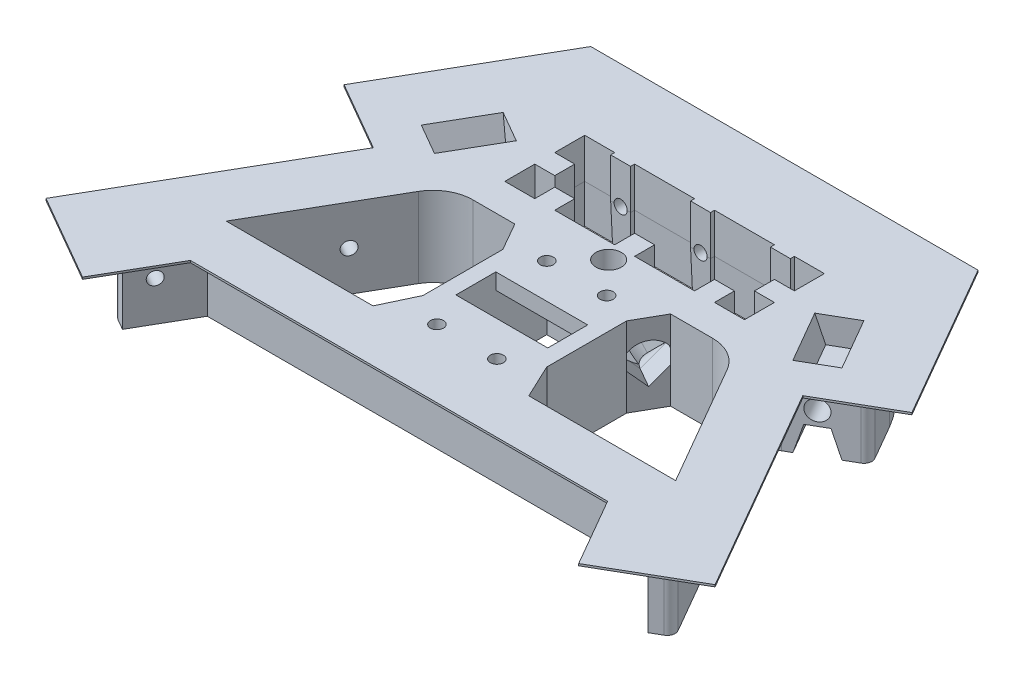
SolidWorks part; units mm, degrees
ref_plane "Front Plane" through (0, 0, 0) normal (0, 0, 1) x (1, 0, 0)
ref_plane "Top Plane" through (0, 0, 0) normal (0, 1, 0) x (1, 0, 0)
ref_plane "Right Plane" through (0, 0, 0) normal (1, 0, 0) x (0, 0, -1)
sketch "Sketch1" plane through (0, 0, 0) normal (0, 1, 0) x (1, 0, 0)
  line L0 (-30, -18) -> (30, -18)
  line L1 (-30, 10) -> (-22.5, 10)
  line L2 (-46.46, 5.4904) -> (-53.96, -7.5) construction
  line L3 (-30, -10) -> (-22.5, -10)
  line L4 (30, 10) -> (30, 2.5)
  line L5 (0, 0) -> (0, -75.5561) construction
  line L6 (38.6603, -23) -> (65.7735, -69.9615)
  line L7 (65.7735, -69.9615) -> (68.3716, -68.4615)
  line L8 (69.1036, -65.7295) -> (41.8357, -18.5)
  line L9 (43.1036, -13.7679) -> (55.6921, -6.5)
  line L10 (56.4241, -3.7679) -> (51.362, 5)
  line L11 (25.3812, 20) -> (-25.3812, 20)
  line L12 (43.5677, -13.5) -> (36.0677, -0.5096) construction
  line L13 (36.0677, -0.5096) -> (46.46, 5.4904) construction
  line L14 (46.46, 5.4904) -> (53.96, -7.5) construction
  line L15 (-36.0677, -0.5096) -> (-46.46, 5.4904) construction
  line L16 (-43.5677, -13.5) -> (-36.0677, -0.5096) construction
  line L17 (-56.4241, -3.7679) -> (-51.362, 5)
  line L18 (-43.1036, -13.7679) -> (-55.6921, -6.5)
  line L19 (-69.1036, -65.7295) -> (-41.8357, -18.5)
  line L20 (-65.7735, -69.9615) -> (-68.3716, -68.4615)
  line L21 (-38.6603, -23) -> (-65.7735, -69.9615)
  line L22 (-30, 10) -> (-30, 2.5)
  line L23 (30, 2.5) -> (25, 2.5)
  line L24 (25, 2.5) -> (25, -2.5)
  line L25 (25, -2.5) -> (30, -2.5)
  line L26 (30, -2.5) -> (30, -10)
  line L27 (22.5, -10) -> (22.5, -5)
  line L28 (22.5, -5) -> (17.5, -5)
  line L29 (17.5, -5) -> (17.5, -10)
  line L30 (22.5, -10) -> (30, -10)
  line L31 (17.5, 10) -> (17.5, 9)
  line L32 (17.5, 9) -> (22.5, 9)
  line L33 (22.5, 9) -> (22.5, 10)
  line L34 (22.5, 10) -> (30, 10)
  line L35 (2.5, -10) -> (2.5, -5)
  line L36 (2.5, -5) -> (-2.5, -5)
  line L37 (-2.5, -5) -> (-2.5, -10)
  line L38 (-2.5, 10) -> (-2.5, 9)
  line L39 (-2.5, 9) -> (2.5, 9)
  line L40 (2.5, 9) -> (2.5, 10)
  line L41 (-17.5, -10) -> (-17.5, -5)
  line L42 (-17.5, -5) -> (-22.5, -5)
  line L43 (-22.5, -5) -> (-22.5, -10)
  line L44 (-22.5, 10) -> (-22.5, 9)
  line L45 (-22.5, 9) -> (-17.5, 9)
  line L46 (-17.5, 9) -> (-17.5, 10)
  line L47 (-17.5, 10) -> (-2.5, 10)
  line L48 (-17.5, -10) -> (-2.5, -10)
  line L49 (2.5, -10) -> (17.5, -10)
  line L50 (2.5, 10) -> (17.5, 10)
  line L51 (-25, -2.5) -> (-30, -2.5)
  line L52 (-25, 2.5) -> (-25, -2.5)
  line L53 (-30, 2.5) -> (-25, 2.5)
  line L54 (-30, -2.5) -> (-30, -10)
  circle A0 centre (0, 0) radius 31.6228 construction
  arc A1 (30, -18) -> (38.6603, -23) centre (30, -28) cw
  arc A2 (51.362, 5) -> (25.3812, 20) centre (25.3812, -10) ccw
  arc A3 (41.1036, -13.7679) -> (40.1036, -17.5) centre (40.1036, -15.5) ccw
  arc A4 (68.3716, -68.4615) -> (69.1036, -65.7295) centre (67.3716, -66.7295) ccw
  arc A5 (55.6921, -6.5) -> (56.4241, -3.7679) centre (54.6921, -4.7679) ccw
  arc A6 (40.1036, -17.5) -> (41.8357, -18.5) centre (40.1036, -19.5) cw
  arc A7 (41.1036, -13.7679) -> (43.1036, -13.7679) centre (42.1036, -12.0359) ccw
  arc A8 (-41.1036, -13.7679) -> (-43.1036, -13.7679) centre (-42.1036, -12.0359) cw
  arc A9 (-40.1036, -17.5) -> (-41.8357, -18.5) centre (-40.1036, -19.5) ccw
  arc A10 (-55.6921, -6.5) -> (-56.4241, -3.7679) centre (-54.6921, -4.7679) cw
  arc A11 (-68.3716, -68.4615) -> (-69.1036, -65.7295) centre (-67.3716, -66.7295) cw
  arc A12 (-41.1036, -13.7679) -> (-40.1036, -17.5) centre (-40.1036, -15.5) cw
  arc A13 (-51.362, 5) -> (-25.3812, 20) centre (-25.3812, -10) cw
  arc A14 (-30, -18) -> (-38.6603, -23) centre (-30, -28) ccw
  point P7 (-57.4241, -5.5)
  point P9 (0, -18)
  point P22 (35.7735, -18)
  point P27 (0, 10)
  point P30 (70.1036, -67.4615)
  point P33 (57.4241, -5.5)
  point P61 (0, 20)
  point P65 (-70.1036, -67.4615)
  point P66 (-35.7735, -18)
  dimension "D12" = 10
  dimension "D14" = 30
  dimension "D16" = 2
  dimension "D17" = 2
  dimension "D2" = 30
  dimension "D3" = 5
  dimension "D4" = 8
  dimension "D5" = 60
  dimension "D6" = 20
  dimension "D7" = 30
  dimension "D8" = 10
  dimension "D9" = 4
  dimension "D10" = 12
  dimension "D11" = 15
  dimension "D13" = 20
  dimension "D18" = 5
  dimension "D19" = 2.5
  dimension "D20" = 5
  dimension "D21" = 5
  dimension "D22" = 5
  dimension "D23" = 7.5
  dimension "D24" = 1
  dimension "D26" = 20
  dimension "D25" = 3
extrude "Boss-Extrude1" add sketch "Sketch1" along normal blind 20
sketch "Sketch2" plane through (16.7376, 0, 28.9904) normal (0.5, 0, 0.866) x (0.866, 0, -0.5)
  line L0 (30.4449, 0) -> (44.9808, 0) construction
  line L1 (26.9808, 20) -> (26.9808, 0) construction
  circle A0 centre (36.9808, 10) radius 5
  dimension "D1" = 10
  dimension "D2" = 10
  dimension "D3" = 10
extrude "Cut-Extrude1" cut sketch "Sketch2" against normal through all
sketch "Sketch3" plane through (16.7376, 0, 28.9904) normal (0.5, 0, 0.866) x (0.866, 0, -0.5)
  circle A0 centre (36.9808, 10) radius 5
  circle A1 centre (36.9808, 10) radius 5 construction
  circle A2 centre (36.9808, 10) radius 2.5
  dimension "D1" = 5
extrude "Boss-Extrude2" add sketch "Sketch3" against normal blind 16
sketch "Sketch4" plane through (16.7376, 0, 28.9904) normal (0.5, 0, 0.866) x (0.866, 0, -0.5)
  line L0 (36.9808, 10) -> (44.9808, 10) construction
  line L1 (44.9808, 20) -> (44.9808, 0) construction
  line L2 (32.4808, 20) -> (34.4808, 13.5)
  line L3 (30.4449, 20) -> (44.9808, 20) construction
  line L4 (34.4808, 13.5) -> (39.4808, 13.5)
  line L5 (39.4808, 13.5) -> (41.4808, 20)
  line L6 (41.4808, 20) -> (32.4808, 20)
  line L7 (36.9808, 13.5) -> (36.9808, 20) construction
  line L8 (41.4808, 0) -> (32.4808, 0)
  line L9 (39.4808, 6.5) -> (41.4808, 0)
  line L10 (34.4808, 6.5) -> (39.4808, 6.5)
  line L11 (32.4808, 0) -> (34.4808, 6.5)
  dimension "D1" = 9
  dimension "D2" = 5
  dimension "D3" = 6.5
extrude "Cut-Extrude2" cut sketch "Sketch4" against normal blind 15
sketch "Sketch7" plane through (0, 0, -20) normal (0, 0, -1) x (-1, 0, 0)
  line L0 (-20, 10) -> (20, 10) construction
  circle A0 centre (-20, 10) radius 1.65
  circle A1 centre (0, 10) radius 1.65
  circle A2 centre (20, 10) radius 1.65
  dimension "D1" = 3.3
  dimension "D3" = 40
  dimension "D4" = 10
  dimension "D2" = 3
extrude "Cut-Extrude4" cut sketch "Sketch7" against normal up to next
sketch "Sketch8" plane through (0, 0, -20) normal (0, 0, -1) x (-1, 0, 0)
  circle A0 centre (-20, 10) radius 6
  circle A1 centre (-20, 10) radius 1.65 construction
  circle A2 centre (0, 10) radius 6
  circle A3 centre (20, 10) radius 6
  circle A4 centre (20, 10) radius 1.65 construction
  dimension "D1" = 12
  dimension "D2" = 3
extrude "Cut-Extrude5" cut sketch "Sketch8" against normal offset from surface (4 mm away) 7 up to face at (1.65, 10, -9)
sketch "Sketch9" plane through (0, 0, 0) normal (0, 1, 0) x (1, 0, 0)
  line L0 (-11.5, -40) -> (11.5, -40) construction
  line L1 (2.5, -10) -> (17.5, -10) construction
  line L2 (-11.5, -30) -> (11.5, -30) construction
  line L3 (-11.5, -30) -> (-11.5, -40)
  line L4 (11.5, -30) -> (11.5, -40)
  line L5 (0, -30) -> (0, 0) construction
  line L6 (-19.5, -18) -> (-15.5, -25)
  line L7 (-30, -18) -> (30, -18) construction
  line L8 (-15.5, -25) -> (-15.5, -45)
  line L9 (-15.5, -45) -> (-19.5, -53.5)
  line L10 (-56.2694, -53.5) -> (-19.5, -53.5)
  line L11 (19.5, -53.5) -> (15.5, -45)
  line L12 (15.5, -45) -> (15.5, -25)
  line L13 (15.5, -25) -> (19.5, -18)
  line L14 (-19.5, -18) -> (-11.5, -18)
  line L15 (-11.5, -35) -> (11.5, -35) construction
  line L16 (11.5, -30) -> (11.5, -18)
  line L17 (-11.5, -30) -> (-11.5, -18)
  line L18 (11.5, -18) -> (19.5, -18)
  line L19 (-11.5, -40) -> (-11.5, -53.5)
  line L20 (-11.5, -53.5) -> (11.5, -53.5)
  line L21 (11.5, -53.5) -> (11.5, -40)
  line L30 (-65.7735, -69.9615) -> (-38.6603, -23) construction
  line L31 (38.6603, -23) -> (65.7735, -69.9615) construction
  line L32 (19.5, -53.5) -> (56.2694, -53.5)
  line L33 (-58.0015, -56.5) -> (58.0015, -56.5)
  line L34 (58.0015, -56.5) -> (56.2694, -53.5)
  line L35 (-58.0015, -56.5) -> (-56.2694, -53.5)
  circle A0 centre (0, -20.5) radius 1.65 construction
  circle A1 centre (0, -49.5) radius 1.65 construction
  dimension "D6" = 3.3
  dimension "D11" = 2.5
  dimension "D1" = 30
  dimension "D2" = 10
  dimension "D3" = 23
  dimension "D4" = 4
  dimension "D5" = 4
  dimension "D7" = 7
  dimension "D8" = 8.5
  dimension "D9" = 7
  dimension "D10" = 20
  dimension "D14" = 4
  dimension "D15" = 4
  dimension "D16" = 4
  dimension "D17" = 3
extrude "Boss-Extrude3" add sketch "Sketch9" along normal up to surface (20 mm away) up to face at (6.0019, 20, 19.8008)
sketch "Sketch11" plane through (23.366, 0, -13.4904) normal (0.866, 0, -0.5) x (-0.5, 0, -0.866)
  line L1 (-81.4752, 12.5) -> (-56.9393, 12.5)
  line L2 (-81.4752, 12.5) -> (-81.4752, 7.5)
  line L3 (-81.4752, 7.5) -> (-56.9393, 7.5)
  line L4 (-36.9393, 12.5) -> (-36.9393, 7.5)
  line L5 (-36.9393, 20) -> (-36.9393, 0) construction
  line L6 (-91.4752, 0) -> (-36.9393, 0) construction
  line L7 (-46.9393, 12.5) -> (-46.9393, 7.5)
  line L8 (-56.9393, 12.5) -> (-56.9393, 7.5)
  line L9 (-46.9393, 12.5) -> (-36.9393, 12.5)
  line L10 (-46.9393, 7.5) -> (-36.9393, 7.5)
  line L11 (-91.4752, 20) -> (-91.4752, 0) construction
  dimension "D1" = 5
  dimension "D2" = 7.5
  dimension "D3" = 10
  dimension "D4" = 10
  dimension "D5" = 10
extrude "Boss-Extrude5" add sketch "Sketch11" along normal blind 3
chamfer "Chamfer1" distance 3 angle 45 4 edges at (44.4338, 10, 17) (49.4338, 10, 25.6603) (54.4338, 10, 34.3205) (66.7017, 10, 55.5692)
sketch "Sketch13" plane through (23.366, 0, -13.4904) normal (0.866, 0, -0.5) x (-0.5, 0, -0.866)
  line L0 (-56.9393, 10) -> (-46.9393, 10) construction
  line L1 (-56.9393, 7.5) -> (-56.9393, 12.5) construction
  line L2 (-46.9393, 12.5) -> (-46.9393, 7.5) construction
  line L3 (-81.4752, 10) -> (-93.4752, 10) construction
  line L4 (-81.4752, 12.5) -> (-81.4752, 7.5) construction
  line L5 (-93.4752, 20) -> (-93.4752, 0) construction
  circle A0 centre (-51.9393, 10) radius 1.65
  circle A1 centre (-87.4752, 10) radius 1.65
  dimension "D1" = 3.3
  dimension "D2" = 3.3
extrude "Cut-Extrude6" cut sketch "Sketch13" against normal up to next
mirror "Mirror2" about plane through (0, 0, 0) normal (1, 0, 0) of "Cut-Extrude6", "Chamfer1", "Boss-Extrude5", "Cut-Extrude2", "Boss-Extrude2", "Cut-Extrude1"
ref_plane "Plane2" through (0, 10, 0) normal (0, 1, 0) x (1, 0, 0)
sketch "Sketch15" plane through (0, 10, 0) normal (0, 1, 0) x (1, 0, 0)
  line L0 (-10, -10) -> (-10, -14.3127)
  line L1 (-17.5, -10) -> (-2.5, -10) construction
  line L2 (-12.5193, -18.6539) -> (-17.5, -21.5)
  line L3 (-19.5, -18) -> (-15.5, -25) construction
  arc A0 (-10, -14.3127) -> (-12.5193, -18.6539) centre (-15, -14.3127) cw
  dimension "D1" = 5
sketch "Sketch16" plane through (0, 0, 10) normal (0, 0, -1) x (-1, 0, 0)
  line L0 (5, 10) -> (10, 5)
  line L1 (10, 5) -> (15, 10)
  arc A0 (15, 10) -> (5, 10) centre (10, 10) ccw
  dimension "D1" = 10
sketch "Sketch17" plane through (0, 20, 0) normal (0, 1, 0) x (1, 0, 0)
  line L0 (-11.5, -53.5) -> (-11.5, -18) construction
  line L1 (11.5, -18) -> (-11.5, -18)
  line L2 (11.5, -18) -> (11.5, -30.75)
  line L3 (11.5, -30.75) -> (-11.5, -30.75)
  line L4 (-11.5, -18) -> (-11.5, -30.75)
  line L5 (-11.5, -18) -> (11.5, -18) construction
  line L6 (11.5, -18) -> (11.5, -53.5) construction
  line L7 (11.5, -53.5) -> (-11.5, -53.5) construction
  line L9 (-11.5, -53.5) -> (11.5, -53.5)
  line L10 (-11.5, -53.5) -> (-11.5, -40.75)
  line L11 (-11.5, -40.75) -> (11.5, -40.75)
  line L12 (11.5, -53.5) -> (11.5, -40.75)
  line L13 (22.5, -10) -> (30, -10) construction
  circle A0 centre (-7.5, -49.5) radius 1.65
  circle A1 centre (7.5, -49.5) radius 1.65
  circle A2 centre (7.5, -22) radius 1.65
  circle A3 centre (-7.5, -22) radius 1.65
  dimension "D3" = 3.3
  dimension "D4" = 4
  dimension "D5" = 4
  dimension "D8" = 4
  dimension "D1" = 10
  dimension "D2" = 30.75
  dimension "D9" = 4
  dimension "D6" = 2
  dimension "D7" = 2
extrude "Boss-Extrude6" add sketch "Sketch17" against normal blind 4 separate body
sweep "Cut-Sweep1" cut profiles "Sketch16" path "Sketch15"
mirror "Mirror3" about plane through (0, 0, 0) normal (1, 0, 0) of "Cut-Sweep1"
sketch "Sketch18" plane through (0, 20, 0) normal (0, 1, 0) x (1, 0, 0)
  line L0 (0, -18) -> (0, -10) construction
  line L1 (-11.5, -18) -> (11.5, -18) construction
  line L2 (2.5, -10) -> (17.5, -10) construction
  circle A0 centre (0, -14) radius 3.2
  dimension "D1" = 6.4
extrude "Cut-Extrude7" cut sketch "Sketch18" against normal blind 10
chamfer "Chamfer3" distance 10 distance2 0.25 36 edges at (26.25, 0, -10) (30, 0, -6.25) (27.5, 0, -2.5) (25, 0, 0) (27.5, 0, 2.5) (30, 0, 6.25) (26.25, 0, 10) (22.5, 0, 7.5) (20, 0, 5) (17.5, 0, 7.5) (10, 0, 10) (2.5, 0, 7.5) (0, 0, 5) (-2.5, 0, 7.5) (-10, 0, 10) (-17.5, 0, 7.5) (-20, 0, 5) (-22.5, 0, 7.5) (-26.25, 0, 10) (-30, 0, 6.25) (-27.5, 0, 2.5) (-25, 0, 0) (-27.5, 0, -2.5) (-30, 0, -6.25) (-26.25, 0, -10) (-22.5, 0, -9.5) (-20, 0, -9) (-17.5, 0, -9.5) (-10, 0, -10) (-2.5, 0, -9.5) (0, 0, -9) (2.5, 0, -9.5) (10, 0, -10) (17.5, 0, -9.5) (20, 0, -9) (22.5, 0, -9.5) first distance on face at (26.25, 10, -10) first distance on face at (30, 10, -6.25) first distance on face at (27.5, 10, -2.5) first distance on face at (25, 10, 0) first distance on face at (27.5, 10, 2.5) first distance on face at (30, 10, 6.25) first distance on face at (26.25, 10, 10) first distance on face at (22.5, 10, 7.5) first distance on face at (20, 10, 5) first distance on face at (17.5, 10, 7.5) first distance on face at (10, 10, 10) first distance on face at (2.5, 10, 7.5) first distance on face at (0, 10, 5) first distance on face at (-2.5, 10, 7.5) first distance on face at (-10, 10, 10) first distance on face at (-17.5, 10, 7.5) first distance on face at (-20, 10, 5) first distance on face at (-22.5, 10, 7.5) first distance on face at (-26.25, 10, 10) first distance on face at (-30, 10, 6.25) first distance on face at (-27.5, 10, 2.5) first distance on face at (-25, 10, 0) first distance on face at (-27.5, 10, -2.5) first distance on face at (-30, 10, -6.25) first distance on face at (-26.25, 10, -10) first distance on face at (-22.5, 10, -9.5) first distance on face at (-18.35, 10, -9) first distance on face at (-17.5, 10, -9.5) first distance on face at (-10, 10, -10) first distance on face at (-2.5, 10, -9.5) first distance on face at (1.65, 10, -9) first distance on face at (2.5, 10, -9.5) first distance on face at (10, 10, -10) first distance on face at (17.5, 10, -9.5) first distance on face at (21.65, 10, -9) first distance on face at (22.5, 10, -9.5)
sketch "Sketch20" plane through (0, 20, 0) normal (0, 1, 0) x (1, 0, 0)
  line L0 (-51.362, 5) -> (-56.4241, -3.7679) construction
  line L1 (-55.6921, -6.5) -> (-52.661, -8.25) construction
  line L2 (-50.9289, -9.25) -> (-52.661, -8.25) construction
  line L3 (-46.5988, -11.75) -> (-50.9289, -9.25) construction
  line L4 (-44.8668, -12.75) -> (-46.5988, -11.75) construction
  line L5 (-44.8668, -12.75) -> (-43.1036, -13.7679) construction
  line L6 (-41.8357, -18.5) -> (-69.1036, -65.7295) construction
  line L7 (25.3812, 20) -> (-25.3812, 20) construction
  line L44 (56.4241, -3.7679) -> (51.362, 5) construction
  line L45 (52.661, -8.25) -> (55.6921, -6.5) construction
  line L46 (50.9289, -9.25) -> (52.661, -8.25) construction
  line L47 (46.5988, -11.75) -> (50.9289, -9.25) construction
  line L48 (44.8668, -12.75) -> (46.5988, -11.75) construction
  line L49 (43.1036, -13.7679) -> (44.8668, -12.75) construction
  line L50 (69.1036, -65.7295) -> (41.8357, -18.5) construction
  line L51 (65.7735, -69.9615) -> (68.3716, -68.4615) construction
  line L52 (58.0015, -56.5) -> (65.7735, -69.9615) construction
  line L53 (-58.0015, -56.5) -> (58.0015, -56.5) construction
  line L54 (-65.7735, -69.9615) -> (-58.0015, -56.5) construction
  line L55 (-68.3716, -68.4615) -> (-65.7735, -69.9615) construction
  line L56 (-51.362, 5) -> (-56.4241, -3.7679)
  line L57 (-55.6921, -6.5) -> (-52.661, -8.25)
  line L58 (-50.9289, -9.25) -> (-52.661, -8.25)
  line L59 (-46.5988, -11.75) -> (-50.9289, -9.25)
  line L60 (-44.8668, -12.75) -> (-46.5988, -11.75)
  line L61 (-44.8668, -12.75) -> (-43.1036, -13.7679)
  line L62 (-41.8357, -18.5) -> (-69.1036, -65.7295)
  line L63 (25.3812, 20) -> (-25.3812, 20)
  line L100 (56.4241, -3.7679) -> (51.362, 5)
  line L101 (52.661, -8.25) -> (55.6921, -6.5)
  line L102 (50.9289, -9.25) -> (52.661, -8.25)
  line L103 (46.5988, -11.75) -> (50.9289, -9.25)
  line L104 (44.8668, -12.75) -> (46.5988, -11.75)
  line L105 (43.1036, -13.7679) -> (44.8668, -12.75)
  line L106 (69.1036, -65.7295) -> (41.8357, -18.5)
  line L107 (65.7735, -69.9615) -> (68.3716, -68.4615)
  line L108 (58.0015, -56.5) -> (65.7735, -69.9615)
  line L109 (-58.0015, -56.5) -> (58.0015, -56.5)
  line L110 (-65.7735, -69.9615) -> (-58.0015, -56.5)
  line L111 (-68.3716, -68.4615) -> (-65.7735, -69.9615)
  line L112 (-83.7639, -71.1218) -> (-62.1132, -83.6218)
  line L113 (-62.1132, -83.6218) -> (-52.228, -66.5)
  line L114 (-52.228, -66.5) -> (52.228, -66.5)
  line L115 (-83.7639, -71.1218) -> (-53.7639, -19.1603)
  line L116 (-53.7639, -19.1603) -> (-71.0844, -9.1603)
  line L117 (-71.0844, -9.1603) -> (-48.4752, 30)
  line L118 (-48.4752, 30) -> (48.4752, 30)
  line L119 (0, 0) -> (0, -66.5) construction
  line L120 (71.0844, -9.1603) -> (48.4752, 30)
  line L121 (53.7639, -19.1603) -> (71.0844, -9.1603)
  line L122 (83.7639, -71.1218) -> (53.7639, -19.1603)
  line L123 (83.7639, -71.1218) -> (62.1132, -83.6218)
  line L124 (62.1132, -83.6218) -> (52.228, -66.5)
  arc A0 (-56.4241, -3.7679) -> (-55.6921, -6.5) centre (-54.6921, -4.7679) ccw construction
  arc A1 (-43.1036, -13.7679) -> (-41.1036, -13.7679) centre (-42.1036, -12.0359) ccw construction
  arc A2 (-40.1036, -17.5) -> (-41.1036, -13.7679) centre (-40.1036, -15.5) ccw construction
  arc A3 (-40.1036, -17.5) -> (-41.8357, -18.5) centre (-40.1036, -19.5) ccw construction
  arc A4 (-25.3812, 20) -> (-51.362, 5) centre (-25.3812, -10) ccw construction
  arc A5 (51.362, 5) -> (25.3812, 20) centre (25.3812, -10) ccw construction
  arc A6 (55.6921, -6.5) -> (56.4241, -3.7679) centre (54.6921, -4.7679) ccw construction
  arc A7 (41.1036, -13.7679) -> (43.1036, -13.7679) centre (42.1036, -12.0359) ccw construction
  arc A8 (41.1036, -13.7679) -> (40.1036, -17.5) centre (40.1036, -15.5) ccw construction
  arc A9 (41.8357, -18.5) -> (40.1036, -17.5) centre (40.1036, -19.5) ccw construction
  arc A10 (68.3716, -68.4615) -> (69.1036, -65.7295) centre (67.3716, -66.7295) ccw construction
  arc A11 (-69.1036, -65.7295) -> (-68.3716, -68.4615) centre (-67.3716, -66.7295) ccw construction
  arc A12 (-56.4241, -3.7679) -> (-55.6921, -6.5) centre (-54.6921, -4.7679) ccw
  arc A13 (-43.1036, -13.7679) -> (-41.1036, -13.7679) centre (-42.1036, -12.0359) ccw
  arc A14 (-40.1036, -17.5) -> (-41.1036, -13.7679) centre (-40.1036, -15.5) ccw
  arc A15 (-40.1036, -17.5) -> (-41.8357, -18.5) centre (-40.1036, -19.5) ccw
  arc A16 (-25.3812, 20) -> (-51.362, 5) centre (-25.3812, -10) ccw
  arc A17 (51.362, 5) -> (25.3812, 20) centre (25.3812, -10) ccw
  arc A18 (55.6921, -6.5) -> (56.4241, -3.7679) centre (54.6921, -4.7679) ccw
  arc A19 (41.1036, -13.7679) -> (43.1036, -13.7679) centre (42.1036, -12.0359) ccw
  arc A20 (41.1036, -13.7679) -> (40.1036, -17.5) centre (40.1036, -15.5) ccw
  arc A21 (41.8357, -18.5) -> (40.1036, -17.5) centre (40.1036, -19.5) ccw
  arc A22 (68.3716, -68.4615) -> (69.1036, -65.7295) centre (67.3716, -66.7295) ccw
  arc A23 (-69.1036, -65.7295) -> (-68.3716, -68.4615) centre (-67.3716, -66.7295) ccw
  point P91 (0, 30)
  dimension "D1" = 10
  dimension "D2" = 10
  dimension "D3" = 10
  dimension "D4" = 10
  dimension "D5" = 10
  dimension "D6" = 10
  dimension "D7" = 10
extrude "Boss-Extrude7" add sketch "Sketch20" against normal blind 0.5
